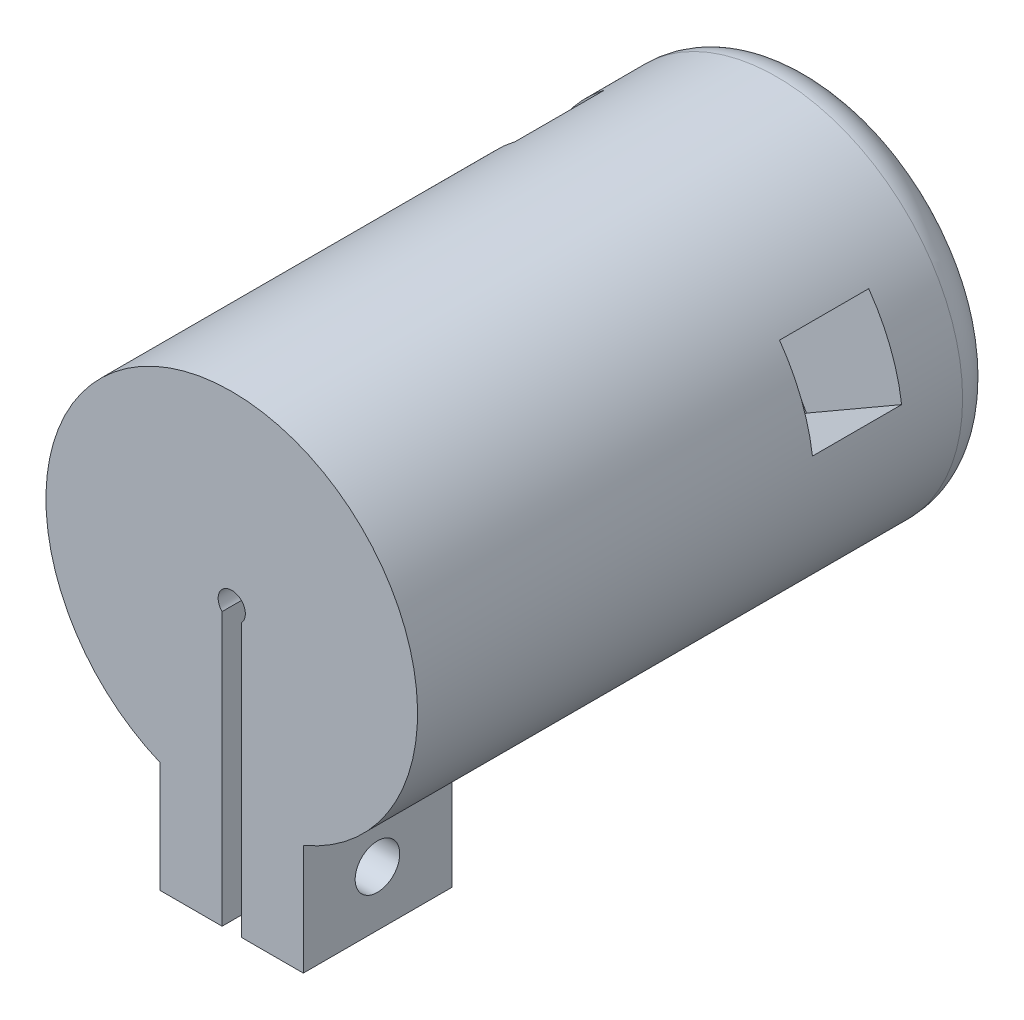
SolidWorks part; units mm, degrees
ref_plane "Front Plane" through (0, 0, 0) normal (0, 0, 1) x (1, 0, 0)
ref_plane "Top Plane" through (0, 0, 0) normal (0, 1, 0) x (1, 0, 0)
ref_plane "Right Plane" through (0, 0, 0) normal (1, 0, 0) x (0, 0, -1)
sketch "Sketch1" plane through (0, 0, 0) normal (0, 0, 1) x (1, 0, 0)
  line L0 (-1.1, 0) -> (1.1, 0) construction
  line L1 (-0.7778, -22.7778) -> (-5.7778, -22.7778)
  line L2 (0, 0) -> (-0.7778, -0.7778) construction
  line L3 (-5.7778, -22.7778) -> (-5.7778, -13.8426)
  line L4 (0.7778, -22.7778) -> (5.7778, -22.7778)
  line L5 (5.7778, -22.7778) -> (5.7778, -13.8426)
  line L6 (0, 0) -> (0.7778, -0.7778) construction
  line L7 (-0.7778, -0.7778) -> (-0.7778, -22.7778)
  line L8 (0.7778, -0.7778) -> (0.7778, -22.7778)
  circle A0 centre (0, 0) radius 15
  circle A1 centre (0, 0) radius 1.1
  dimension "D1" = 2.2
  dimension "D2" = 30
  dimension "D3" = 45
  dimension "D4" = 5
  dimension "D5" = 5
  dimension "D6" = 22
  dimension "D7" = 22
extrude "Boss-Extrude1" add sketch "Sketch1" along normal blind 12 contours A1 L8 A0 L7 | A0 L3 L1 L7 | A0 L8 L4 L5 region at (-3.3351, -18.6633, 0) region at (-3.2327, -14.2129, 0) region at (3.3351, -18.6633, 0)
extrude "Boss-Extrude2" add sketch "Sketch1<4>" against normal blind 35 contours A1 L8 A0 L7 | A1 L7 A0 L8 | A1 region at (-3.2327, -14.2129, 0) region at (0, -7.9962, 0) region at (0, 0, 0)
sketch "Sketch1<4>" plane through (0, 0, 0) normal (0, 0, 1) x (1, 0, 0) same geometry as "Sketch1"
ref_plane "Plane1" through (0, 0, -25) normal (0, 0, -1) x (-1, 0, 0)
sketch "Sketch2" plane through (0, 0, -25) normal (0, 0, -1) x (-1, 0, 0)
  line L0 (0, 0) -> (0, -15)
  line L1 (-14.1148, 5.0768) -> (0, 0)
  line L2 (0, 0) -> (11.454, 9.6854)
  line L3 (0, 15) -> (0, -15) construction
  circle A0 centre (0, 0) radius 15 construction
  circle A1 centre (0, 0) radius 15
  dimension "D1" = 109.782
  dimension "D2" = 120
ref_plane "Plane2" through (0, -14.9798, 0) normal (0, -1, 0) x (-1, 0, 0)
sketch "Sketch4" plane through (0, -14.9798, 0) normal (0, -1, 0) x (-1, 0, 0)
  line L0 (5.7778, 0) -> (0.7778, 0) construction
  line L1 (5.7778, 27.2) -> (-1.4222, 27.2)
  line L2 (5.7778, 27.2) -> (5.7778, 20)
  line L3 (5.7778, 20) -> (-1.4222, 20)
  line L4 (-1.4222, 27.2) -> (-1.4222, 20)
  line L5 (5.7778, 0) -> (0.7778, 0)
  dimension "D1" = 7.2
  dimension "D2" = 7.2
  dimension "D3" = 20
  dimension "D4" = 0
extrude "Cut-Extrude1" cut sketch "Sketch4" against normal blind 10 and the other way blind 10 contours L1 L4 L3 L2 region at (-2.1778, -14.9798, -23.6)
ref_axis "Eix de revolució" through (0, 0, 12) along (0, 0, -1)
pattern_circular "CirPattern1" count 3 over 360 about axis through (0, 0, 12) along (0, 0, -1) of "Cut-Extrude1"
fillet "Fillet1" radius 3 1 edges at (15, 0, -35) type face fillet first side face at (15, 0, -35) second side face at (13.7577, 5.3895, -23.6)
sketch "Sketch11" plane through (-5.7778, 0, 0) normal (-1, 0, 0) x (0, 0, 1)
  line L0 (0, -13.8426) -> (12, -22.7778) construction
  line L1 (0, -22.7778) -> (12, -13.8426) construction
  line L2 (12, -22.7778) -> (12, -13.8426) construction
hole_wizard "CSK for M3 Oval Head Machine Screw1" positions "Sketch15" profile "Sketch13" countersink size "M3" standard "ANSI Metric" end condition through all
sketch "Sketch15" plane through (-5.7778, 0, 0) normal (-1, 0, 0) x (0, 0, 1)
  point P0 (6.0161, -18.3217)
sketch "Sketch13" plane through (-5.7778, -18.3217, 6.0161) normal (0, 1, 0) x (0, 0, 1)
  line L0 (0, 0) -> (0, 20.7778)
  line L1 (0, 20.7778) -> (1.8, 20.7778)
  line L2 (1.8, 20.7778) -> (1.8, 1.35)
  line L3 (1.8, 1.35) -> (3.15, 0)
  line L5 (3.15, 0) -> (0, 0)
  line L6 (-1.8, 1.35) -> (-3.15, 0) construction
  line L11 (0, -6.35) -> (0, 107.95) construction
  dimension "Thru Hole Dia." = 3.6
  dimension "Thru Hole Depth" = 20.7778
  dimension "Near C'Sink Dia." = 6.3
  dimension "Near C'Sink Angle" = 90
